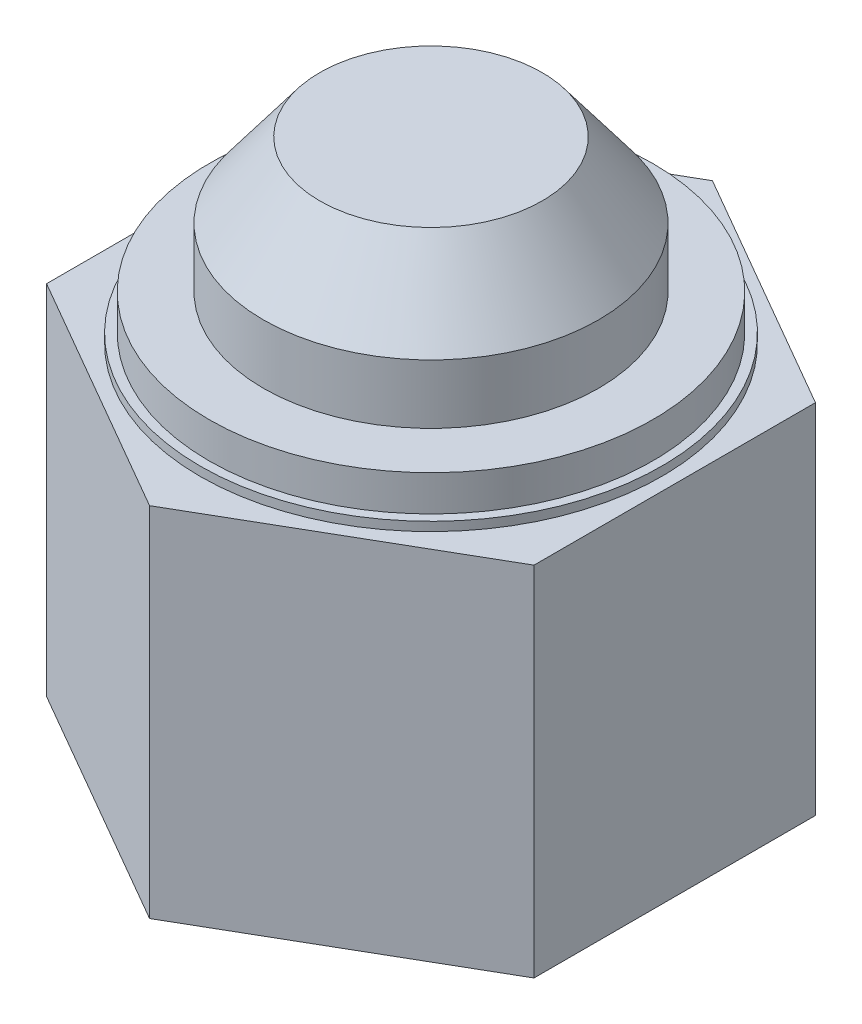
SolidWorks part; units mm, degrees
ref_plane "Front Plane" through (0, 0, 0) normal (0, 0, 1) x (1, 0, 0)
ref_plane "Top Plane" through (0, 0, 0) normal (0, 1, 0) x (1, 0, 0)
ref_plane "Right Plane" through (0, 0, 0) normal (1, 0, 0) x (0, 0, -1)
sketch "Sketch1" plane through (0, 0, 0) normal (0, 1, 0) x (1, 0, 0)
  line L1 (0, 7.9969) -> (-6.9255, 3.9984)
  line L2 (-6.9255, 3.9984) -> (-6.9255, -3.9984)
  line L3 (-6.9255, -3.9984) -> (0, -7.9969)
  line L4 (0, -7.9969) -> (6.9255, -3.9984)
  line L5 (6.9255, -3.9984) -> (6.9255, 3.9984)
  line L6 (6.9255, 3.9984) -> (0, 7.9969)
  circle A0 centre (0, 0) radius 4.7625
  circle A1 centre (0, 0) radius 6.35
  circle A2 centre (0, 0) radius 7.9969
  circle A3 centre (0, 0) radius 6.9255 construction
  circle A4 centre (0, 0) radius 8.8049
  dimension "D1" = 9.525
  dimension "D2" = 12.7
extrude "Boss-Extrude1" add sketch "Sketch1" along normal blind 5.08 contours A0 A1 region at (0, 0, 0)
sketch "Sketch2" plane through (0, 0, 0) normal (0, -1, 0) x (1, 0, 0)
  circle A0 centre (0, 0) radius 3.175
  circle A1 centre (0, 0) radius 4.7625
  dimension "D1" = 6.35
  dimension "D2" = 9.525
sketch "Sketch5" plane through (0, 0, 0) normal (0, -1, 0) x (1, 0, 0)
  circle A0 centre (0, 0) radius 3.175
sketch "Sketch6" plane through (0, 5.08, 0) normal (0, 1, 0) x (1, 0, 0)
  circle A0 centre (0, 0) radius 4.7625
  circle A3 centre (0, 0) radius 3.175
  dimension "D1" = 9.525
extrude "Boss-Extrude4" add sketch "Sketch1<4>" against normal blind 10.16 separate body contours L5 L6 L1 L2 L3 L4 A1 region at (3.357, 0, -5.8144)
sketch "Sketch1<4>" plane through (0, 0, 0) normal (0, 1, 0) x (1, 0, 0) same geometry as "Sketch1"
sketch "Sketch3" plane through (0, 5.08, 0) normal (0, 1, 0) x (1, 0, 0)
  line L1 (0, 4.7625) -> (-4.1244, 2.3812)
  line L2 (-4.1244, 2.3812) -> (-4.1244, -2.3813)
  line L3 (-4.1244, -2.3813) -> (0, -4.7625)
  line L4 (0, -4.7625) -> (4.1244, -2.3812)
  line L5 (4.1244, -2.3812) -> (4.1244, 2.3813)
  line L6 (4.1244, 2.3813) -> (0, 4.7625)
  circle A0 centre (0, 0) radius 4.7625
  circle A1 centre (0, 0) radius 4.1244 construction
  circle A2 centre (0, 0) radius 6.6996
sketch "Sketch7" plane through (0, 0, 0) normal (0, 1, 0) x (1, 0, 0)
  circle A0 centre (0, 0) radius 6.3042
extrude "Boss-Extrude5" add sketch "Sketch7" along normal blind 1.27
chamfer "Chamfer1" distance 2.126 angle 37 1 edges at (0, 5.08, 4.7625) first distance on face at (0, 1.27, 4.7625)
sketch "Sketch8" plane through (0, 0, 0) normal (0, 1, 0) x (1, 0, 0)
  circle A0 centre (0, 0) radius 6.5595
extrude "Boss-Extrude6" add sketch "Sketch8" along normal blind 0.254
